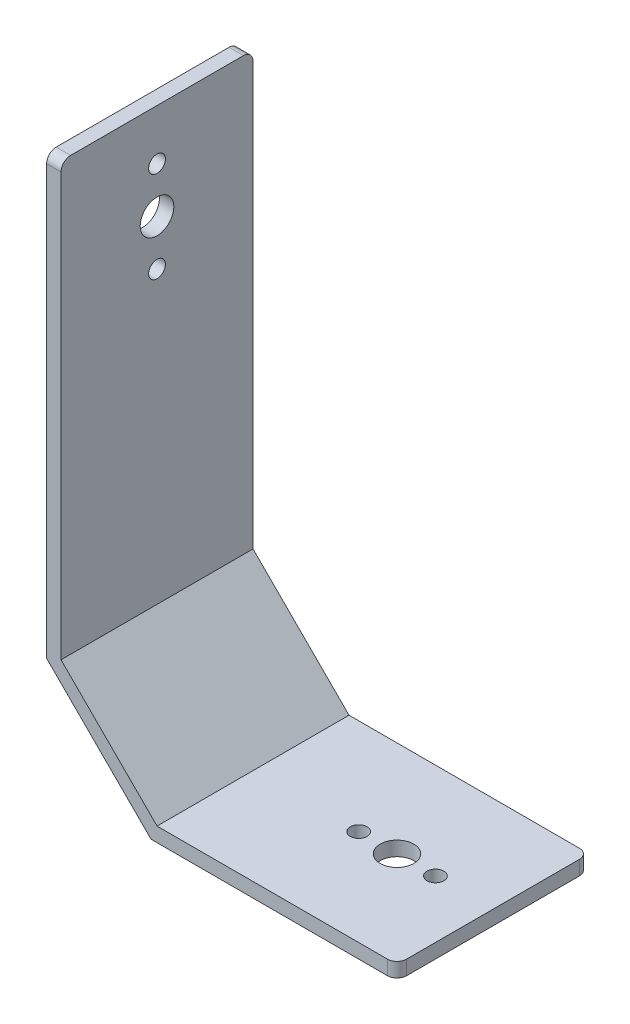
SolidWorks part; units mm, degrees
ref_plane "Plan de face" through (0, 0, 0) normal (0, 0, 1) x (1, 0, 0)
ref_plane "Plan de dessus" through (0, 0, 0) normal (0, 1, 0) x (1, 0, 0)
ref_plane "Plan de droite" through (0, 0, 0) normal (1, 0, 0) x (0, 0, -1)
sketch "Esquisse1" plane through (0, 0, 0) normal (0, 0, 1) x (1, 0, 0)
  line L0 (0, 0) -> (0, 90)
  line L1 (20, -20) -> (70, -20)
  line L2 (0, 0) -> (20, -20)
  dimension "D1" = 50
  dimension "D2" = 90
  dimension "D3" = 20
  dimension "D4" = 20
extrude "Extru.-Mince1" add sketch "Esquisse1" along normal blind 40 thin thin type one direction wall 3
sketch "Esquisse2" plane through (0, 0, 0) normal (1, 0, 0) x (0, 0, -1)
  line L0 (-36.8852, 70) -> (-4.765, 70) construction
  line L1 (-20, 88.5735) -> (-20, 46.5374) construction
  line L2 (0, 90) -> (0, 0) construction
  line L3 (-40, 90) -> (0, 90) construction
  circle A0 centre (-20, 79.5) radius 1.75
  circle A1 centre (-20, 60.5) radius 1.75
  circle A4 centre (-20, 70) radius 3.5
  dimension "D5" = 3.5
  dimension "D8" = 3.5
  dimension "D11" = 7
  dimension "D1" = 9.5
  dimension "D2" = 9.5
  dimension "D9" = 20
  dimension "D10" = 20
extrude "Enlèv. mat.-Extru.1" cut sketch "Esquisse2" against normal blind 3
fillet "Congé3" radius 2 1 edges at (-1.5, 90, 40)
fillet "Congé4" radius 2 1 edges at (-1.5, 90, 0)
fillet "Congé5" radius 2 1 edges at (70, -21.5, 40)
fillet "Congé6" radius 2 1 edges at (70, -21.5, 0)
sketch "Esquisse3" plane through (0, 0, 0) normal (0, 1, 0) x (1, 0, 0)
  line L0 (58, -20) -> (75.235, -20) construction
  line L1 (50, -5.0415) -> (50, -47.0776) construction
  line L4 (70, -38) -> (70, -2) construction
  line L5 (20, -40) -> (68, -40) construction
  circle A2 centre (58, -20) radius 1.75
  circle A3 centre (42, -20) radius 1.75
  circle A4 centre (50, -20) radius 3.5
  dimension "D6" = 3.5
  dimension "D7" = 3.5
  dimension "D9" = 7
  dimension "D3" = 8
  dimension "D4" = 8
  dimension "D10" = 20
  dimension "D11" = 20
extrude "Enlèv. mat.-Extru.2" cut sketch "Esquisse3" against normal blind 50
